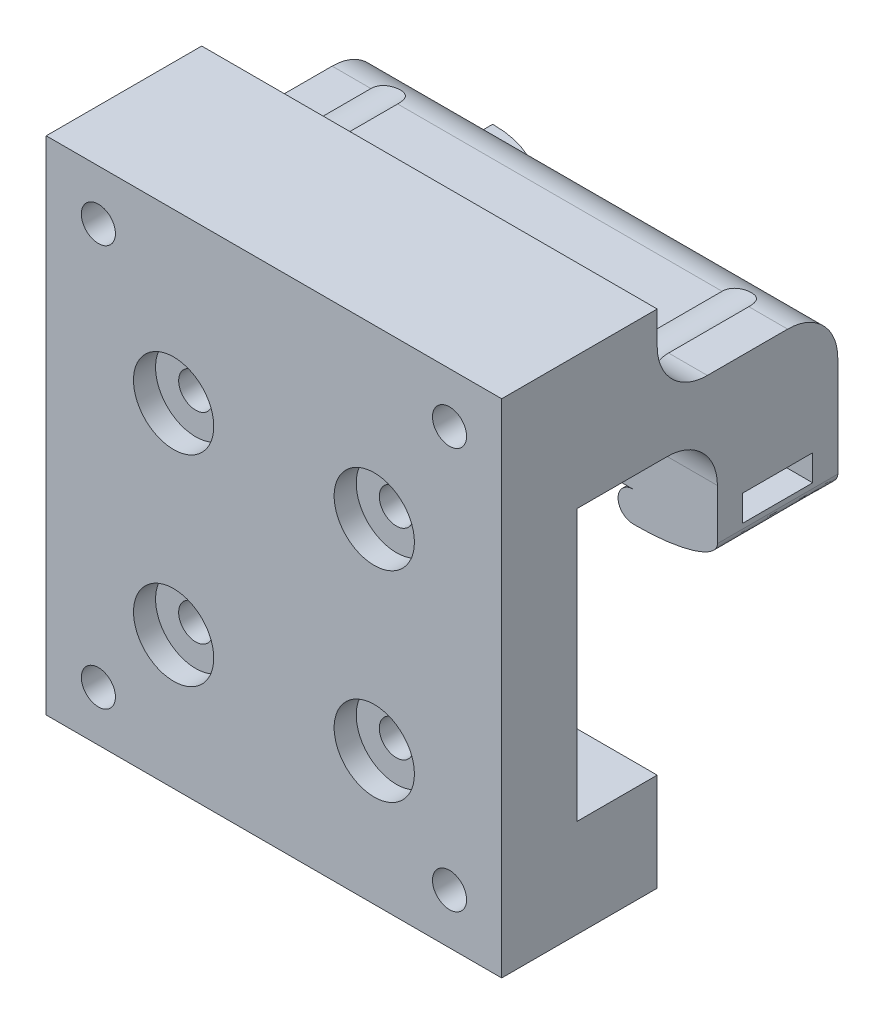
SolidWorks part; units mm, degrees
ref_plane "Front Plane" through (0, 0, 0) normal (0, 0, 1) x (1, 0, 0)
ref_plane "Top Plane" through (0, 0, 0) normal (0, 1, 0) x (1, 0, 0)
ref_plane "Right Plane" through (0, 0, 0) normal (1, 0, 0) x (0, 0, -1)
sketch "Sketch1" plane through (0, 0, 0) normal (0, 0, 1) x (1, 0, 0)
  line L1 (0, 0) -> (45.4, 0)
  line L2 (0, 0) -> (0, 50)
  line L3 (0, 50) -> (45.4, 50)
  line L4 (45.4, 0) -> (45.4, 50)
  dimension "D1" = 45.4
  dimension "D2" = 50
extrude "Boss-Extrude1" add sketch "Sketch1" along normal blind 15.5
sketch "Sketch2" plane through (0, 0, 0) normal (0, 0, -1) x (-1, 0, 0)
  line L0 (-45.4, 0) -> (-45.4, 50) construction
  line L1 (-45.4, 36.7633) -> (0, 36.7633)
  line L2 (-45.4, 36.7633) -> (-45.4, 9.7633)
  line L3 (-45.4, 9.7633) -> (0, 9.7633)
  line L4 (0, 36.7633) -> (0, 9.7633)
  line L5 (0, 50) -> (0, 0) construction
  dimension "D1" = 27
extrude "Cut-Extrude1" cut sketch "Sketch2" against normal blind 8
sketch "Sketch7" plane through (0, 0, 0) normal (0, 0, -1) x (-1, 0, 0)
  line L1 (-45.4, 41.7633) -> (0, 41.7633)
  line L2 (-45.4, 41.7633) -> (-45.4, 36.7633)
  line L3 (-45.4, 36.7633) -> (0, 36.7633)
  line L4 (0, 41.7633) -> (0, 36.7633)
  dimension "D1" = 5
extrude "Boss-Extrude2" add sketch "Sketch7" along normal blind 18
sketch "Sketch8" plane through (0, 36.7633, 0) normal (0, -1, 0) x (1, 0, 0)
  line L1 (0, -18) -> (45.4, -18)
  line L2 (0, -18) -> (0, -6)
  line L3 (0, -6) -> (45.4, -6)
  line L4 (45.4, -18) -> (45.4, -6)
  line L5 (45.4, -18) -> (45.4, 0) construction
  dimension "D1" = 12
extrude "Boss-Extrude3" add sketch "Sketch8" along normal blind 12.52
sketch "Sketch10" plane through (0, 0, -18) normal (0, 0, -1) x (-1, 0, 0)
  line L0 (0, 27.2433) -> (-45.4, 27.2433) construction
  line L1 (0, 24.2433) -> (0, 41.7633) construction
  line L2 (-45.4, 41.7633) -> (-45.4, 24.2433) construction
  line L3 (0, 24.2433) -> (-45.4, 24.2433) construction
  line L5 (-37, 27.2433) -> (-8, 27.2433)
  line L7 (-37, 24.2433) -> (-8, 24.2433)
  arc A0 (-37, 27.2433) -> (-37, 24.2433) centre (-37, 25.7433) cw
  arc A1 (-8, 27.2433) -> (-8, 24.2433) centre (-8, 25.7433) ccw
  dimension "D1" = 3
extrude "Cut-Extrude2" cut sketch "Sketch10" against normal up to next
sketch "Sketch11" plane through (45.4, 0, 0) normal (1, 0, 0) x (0, 0, -1)
  line L1 (8.5, 27.2433) -> (15.5, 27.2433)
  line L2 (8.5, 27.2433) -> (8.5, 29.8433)
  line L3 (8.5, 29.8433) -> (15.5, 29.8433)
  line L4 (15.5, 27.2433) -> (15.5, 29.8433)
  line L5 (6, 24.2433) -> (6, 36.7633) construction
  line L6 (18, 41.7633) -> (18, 24.2433) construction
  line L7 (18, 24.2433) -> (6, 24.2433) construction
  dimension "D1" = 2.5
  dimension "D2" = 2.5
  dimension "D3" = 2.6
  dimension "D4" = 3
extrude "Cut-Extrude3" cut sketch "Sketch11" against normal through all
fillet "Fillet1" radius 2.5 2 edges at (0, 24.2433, -12) (45.4, 24.2433, -12) second distance 8 first distance on face at (0, 28.5433, -12) first distance on face at (45.4, 28.5433, -12)
sketch "Sketch13" plane through (0, 0, 15.5) normal (0, 0, 1) x (1, 0, 0)
  circle A0 centre (12.7, 33.2632) radius 1.7
  circle A1 centre (32.7, 33.2632) radius 1.7
  circle A2 centre (32.7, 13.2632) radius 1.7
  circle A3 centre (12.7, 13.2632) radius 1.7
  dimension "D1" = 3.4
extrude "Cut-Extrude4" cut sketch "Sketch13" against normal up to next
sketch "Sketch14" plane through (0, 0, -18) normal (0, 0, -1) x (-1, 0, 0)
  line L0 (0, 26.7433) -> (0, 41.7633) construction
  line L1 (0, 28.7433) -> (-8, 28.7433)
  line L2 (0, 28.7433) -> (0, 27.2433)
  line L3 (0, 27.2433) -> (-8, 27.2433)
  line L4 (-8, 28.7433) -> (-8, 27.2433)
  line L5 (0, 28.7433) -> (-8, 27.2433) construction
  line L6 (0, 27.2433) -> (-8, 28.7433) construction
  line L7 (-8, 27.2433) -> (-37, 27.2433) construction
  point P4 (-4, 27.9933)
  dimension "D1" = 1.5
  dimension "D2" = 8
extrude "Boss-Extrude4" add sketch "Sketch14" along normal blind 11
fillet "Fillet3" radius 10 1 edges at (8, 27.9933, -18)
fillet "Fillet4" radius 10 1 edges at (8, 27.9933, -29)
sketch "Sketch15" plane through (0, 0, 15.5) normal (0, 0, -1) x (-1, 0, 0)
  line L0 (-22.7, 50) -> (-22.7, 0) construction
  line L1 (-40.2, 5) -> (-5.2, 5) construction
  line L2 (-40.2, 5) -> (-40.2, 45) construction
  line L3 (-40.2, 45) -> (-5.2, 45) construction
  line L4 (-5.2, 5) -> (-5.2, 45) construction
  line L5 (-40.2, 5) -> (-5.2, 45) construction
  line L6 (-40.2, 45) -> (-5.2, 5) construction
  line L7 (-45.4, 50) -> (0, 50) construction
  line L8 (0, 0) -> (-45.4, 0) construction
  line L9 (0, 25) -> (-45.4, 25) construction
  line L12 (0, 50) -> (0, 0) construction
  line L13 (-45.4, 0) -> (-45.4, 50) construction
  circle A0 centre (-5.2, 45) radius 1.7
  circle A1 centre (-40.2, 45) radius 1.7
  circle A2 centre (-40.2, 5) radius 1.7
  circle A3 centre (-5.2, 5) radius 1.7
  point P4 (-22.7, 25)
  dimension "D3" = 3.4
  dimension "D1" = 40
  dimension "D2" = 35
extrude "Cut-Extrude6" cut sketch "Sketch15" along normal through all
ref_plane "Plane1" through (0, 0, 12.5) normal (0, 0, 1) x (1, 0, 0)
sketch "Sketch16" plane through (0, 0, 12.5) normal (0, 0, 1) x (1, 0, 0)
  circle A0 centre (5.2, 45) radius 3.5
  circle A1 centre (40.2, 45) radius 3.5
  circle A2 centre (40.2, 5) radius 3.5
  circle A3 centre (5.2, 5) radius 3.5
  dimension "D1" = 7
extrude "Cut-Extrude7" cut sketch "Sketch16" against normal through all
sketch "Sketch17" plane through (0, 0, 15.5) normal (0, 0, 1) x (1, 0, 0)
  circle A0 centre (12.7, 33.2632) radius 4
  circle A1 centre (32.7, 33.2632) radius 4
  circle A2 centre (32.7, 13.2632) radius 4
  circle A3 centre (12.7, 13.2632) radius 4
  dimension "D1" = 8
extrude "Cut-Extrude8" cut sketch "Sketch17" against normal blind 2.2
fillet "Fillet5" radius 5 1 edges at (22.7, 36.7633, -6)
fillet "Fillet6" radius 5 1 edges at (22.7, 41.7633, -18)
fillet "Fillet7" radius 5 3 edges at (1.9341, 41.7633, 0) (43.4659, 41.7633, 0) (22.7, 41.7633, 0)
sketch "Sketch18" plane through (0, 0, 0) normal (0, 0, -1) x (-1, 0, 0)
  line L0 (-45.4, 4.8816) -> (0, 4.8816) construction
  line L1 (-45.4, 0) -> (-45.4, 9.7633) construction
  line L2 (0, 9.7633) -> (0, 0) construction
  circle A0 centre (-32.4, 4.8816) radius 1.35
  circle A1 centre (-13, 4.8816) radius 1.35
  dimension "D1" = 2.7
  dimension "D2" = 13
  dimension "D3" = 13
extrude "Cut-Extrude9" cut sketch "Sketch18" against normal blind 10
